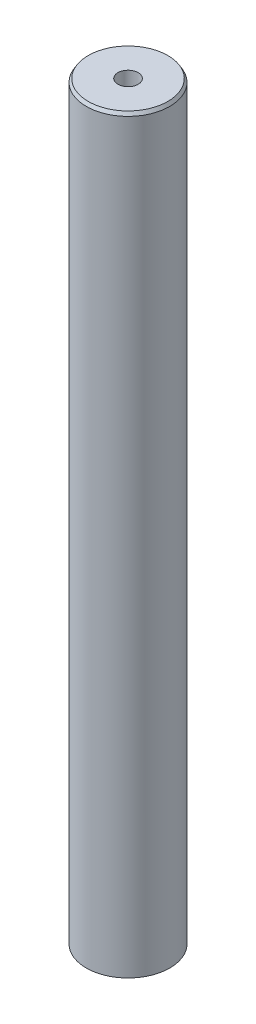
SolidWorks part; units mm, degrees
ref_plane "Front Plane" through (0, 0, 0) normal (0, 0, 1) x (1, 0, 0)
ref_plane "Top Plane" through (0, 0, 0) normal (0, 1, 0) x (1, 0, 0)
ref_plane "Right Plane" through (0, 0, 0) normal (1, 0, 0) x (0, 0, -1)
sketch "Sketch1" plane through (0, 0, 0) normal (0, 1, 0) x (1, 0, 0)
  circle A0 centre (0, 0) radius 5
  dimension "SHAFT_OD" = 10
extrude "Boss-Extrude1" add sketch "Sketch1" along normal blind 90.0144
sketch "Sketch2" plane through (0, 0, 0) normal (0, 1, 0) x (1, 0, 0)
  circle A0 centre (0, 0) radius 1.2127
  dimension "BORE_D" = 2.4255
extrude "Cut-Extrude1" cut sketch "Sketch2" along normal through all
chamfer "Chamfer1" distance 0.4007 angle 30 2 edges at (0, 90.0144, 5) (0, 0, 5) first distance on face at (0, 90.0144, 5) first distance on face at (0, 0, 1.2127)
